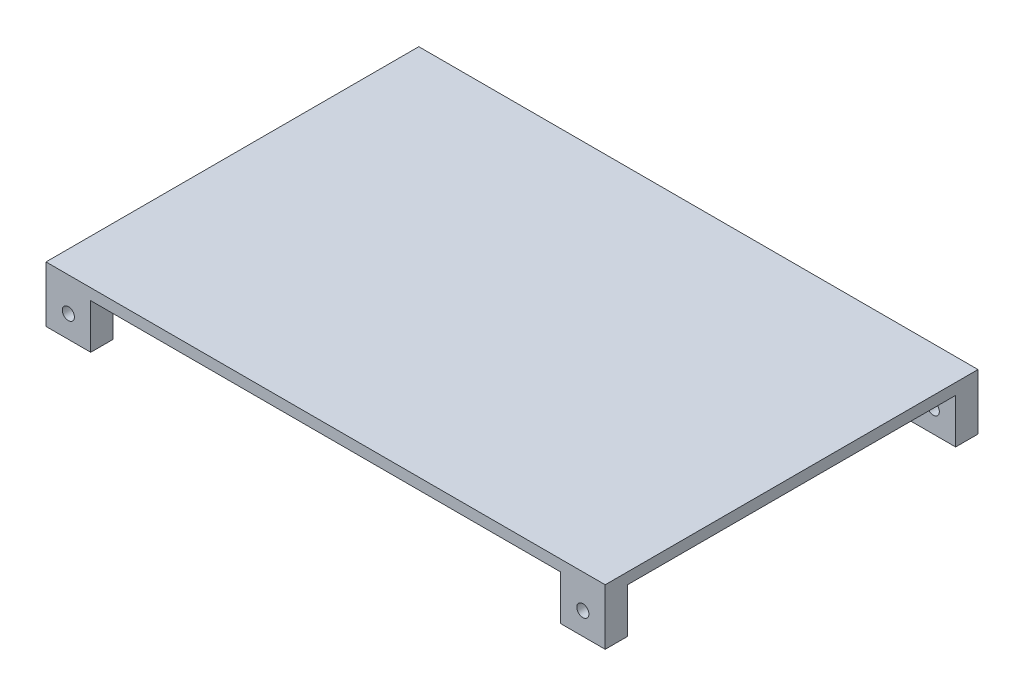
SolidWorks part; units mm, degrees
ref_plane "Front Plane" through (0, 0, 0) normal (0, 0, 1) x (1, 0, 0)
ref_plane "Top Plane" through (0, 0, 0) normal (0, 1, 0) x (1, 0, 0)
ref_plane "Right Plane" through (0, 0, 0) normal (1, 0, 0) x (0, 0, -1)
sketch "Sketch1" plane through (0, 0, 0) normal (0, 1, 0) x (1, 0, 0)
  line L1 (0, 0) -> (150, 0)
  line L2 (0, 0) -> (0, 100)
  line L3 (0, 100) -> (150, 100)
  line L4 (150, 0) -> (150, 100)
  dimension "D1" = 150
  dimension "D2" = 100
extrude "Boss-Extrude1" add sketch "Sketch1" along normal blind 3
sketch "Sketch2" plane through (0, 0, 0) normal (0, -1, 0) x (1, 0, 0)
  line L0 (75, 0) -> (75, -100) construction
  line L1 (0, 0) -> (12, 0)
  line L2 (0, 0) -> (0, -6)
  line L3 (0, -6) -> (12, -6)
  line L4 (12, 0) -> (12, -6)
  line L5 (0, 0) -> (150, 0) construction
  line L6 (150, -100) -> (0, -100) construction
  line L7 (150, -6) -> (138, -6)
  line L8 (138, 0) -> (138, -6)
  line L9 (150, 0) -> (138, 0)
  line L10 (150, 0) -> (150, -6)
  line L11 (0, -50) -> (150, -50) construction
  line L12 (0, -100) -> (0, 0) construction
  line L13 (150, 0) -> (150, -100) construction
  line L14 (150, -100) -> (150, -94)
  line L15 (150, -100) -> (138, -100)
  line L16 (138, -100) -> (138, -94)
  line L17 (150, -94) -> (138, -94)
  line L18 (0, -94) -> (12, -94)
  line L19 (12, -100) -> (12, -94)
  line L20 (0, -100) -> (12, -100)
  line L21 (0, -100) -> (0, -94)
  dimension "D1" = 6
  dimension "D2" = 12
extrude "Boss-Extrude2" add sketch "Sketch2" along normal blind 12
sketch "Sketch4" plane through (0, 0, 0) normal (0, 0, 1) x (1, 0, 0)
  line L0 (12, -12) -> (12, 0) construction
  line L1 (12, -12) -> (0, -12) construction
  line L2 (75, 3) -> (75, 0) construction
  line L3 (0, 3) -> (150, 3) construction
  line L4 (12, 0) -> (138, 0) construction
  circle A0 centre (6, -6) radius 1.625
  circle A1 centre (144, -6) radius 1.625
  dimension "D1" = 3.25
  dimension "D2" = 6
  dimension "D3" = 6
extrude "Cut-Extrude1" cut sketch "Sketch4" against normal through all
